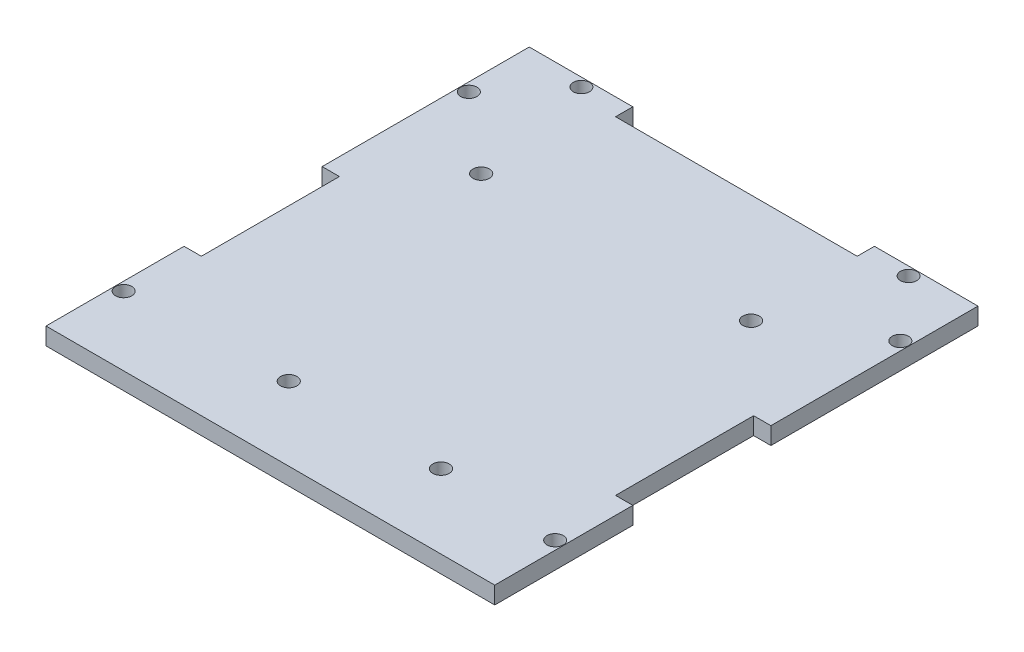
SolidWorks part; units mm, degrees
ref_plane "Front Plane" through (0, 0, 0) normal (0, 0, 1) x (1, 0, 0)
ref_plane "Top Plane" through (0, 0, 0) normal (0, 1, 0) x (1, 0, 0)
ref_plane "Right Plane" through (0, 0, 0) normal (1, 0, 0) x (0, 0, -1)
sketch "Sketch1" plane through (0, 0, 0) normal (0, 1, 0) x (1, 0, 0)
  line L0 (-41.275, 0) -> (-36.3683, -11.7139)
  line L1 (-10.2051, 85.725) -> (10.2051, 85.725)
  line L3 (-41.275, 88.9) -> (-22.225, 88.9)
  line L4 (22.225, 88.9) -> (22.225, 85.725)
  line L5 (41.275, 50.8) -> (41.275, 88.9)
  line L6 (-41.275, 0) -> (-38.1, 0) construction
  line L7 (-41.275, 50.8) -> (-38.1, 50.8)
  line L8 (0, 63.5) -> (0, -63.5) construction
  line L9 (38.1, 50.8) -> (38.1, 25.4)
  line L10 (-38.1, 50.8) -> (-38.1, 25.4)
  line L11 (-41.275, 50.8) -> (-41.275, 88.9)
  line L12 (41.275, 50.8) -> (38.1, 50.8)
  line L13 (-22.225, 88.9) -> (-22.225, 85.725)
  line L14 (-22.225, 85.725) -> (-10.2051, 85.725)
  line L16 (41.275, 88.9) -> (22.225, 88.9)
  line L17 (-41.275, 0) -> (41.275, 0) construction
  line L18 (-38.1, 0) -> (-38.1, 25.4) construction
  line L19 (-38.1, 25.4) -> (-41.275, 25.4)
  line L21 (-41.275, 0) -> (-41.275, 25.4)
  line L22 (38.1, 25.4) -> (41.275, 25.4)
  line L23 (-38.1, 0) -> (-33.467, -10.4244) construction
  line L24 (41.275, 0) -> (41.275, 25.4)
  line L25 (33.467, -10.4244) -> (38.1, 0) construction
  line L26 (-36.3683, -11.7139) -> (-33.467, -10.4244) construction
  line L27 (41.275, 0) -> (36.3683, -11.7139)
  line L28 (36.3683, -11.7139) -> (33.467, -10.4244) construction
  line L29 (-17.858, -45.5446) -> (-12.7, -57.15) construction
  line L30 (-12.7, -57.15) -> (-15.6014, -58.4395) construction
  line L31 (-17.858, -45.5446) -> (-20.7593, -46.8341)
  line L32 (-15.6014, -58.4395) -> (-20.7593, -46.8341)
  line L33 (12.7, -57.15) -> (17.858, -45.5446) construction
  line L34 (-33.467, -10.4244) -> (-17.858, -45.5446)
  line L35 (-12.7, -57.15) -> (12.7, -57.15) construction
  line L36 (17.858, -45.5446) -> (33.467, -10.4244)
  line L38 (41.275, 69.85) -> (-41.275, 69.85) construction
  line L39 (12.7, -57.15) -> (15.6014, -58.4395) construction
  line L40 (17.858, -45.5446) -> (20.7593, -46.8341)
  line L41 (15.6014, -58.4395) -> (20.7593, -46.8341)
  line L42 (38.1, 0) -> (38.1, 25.4) construction
  line L43 (-15.6014, -58.4395) -> (-12.7, -60.325)
  line L44 (-5.08, -57.15) -> (-12.7, -57.15) construction
  line L45 (-5.08, -57.15) -> (-5.08, -60.325)
  line L46 (-5.08, -60.325) -> (-12.7, -60.325)
  line L47 (-12.7, -57.15) -> (-12.7, -60.325) construction
  line L48 (5.08, -57.15) -> (12.7, -57.15) construction
  line L49 (5.08, -57.15) -> (5.08, -60.325)
  line L50 (5.08, -60.325) -> (12.7, -60.325)
  line L51 (12.7, -57.15) -> (12.7, -60.325) construction
  line L52 (15.6014, -58.4395) -> (12.7, -60.325)
  line L53 (-5.08, -57.15) -> (5.08, -57.15)
  line L54 (33.467, -10.4244) -> (36.3683, -11.7139)
  line L55 (-33.467, -10.4244) -> (-36.3683, -11.7139)
  line L56 (10.2051, 85.725) -> (22.225, 85.725)
  point P0 (0, 0)
  point P1 (0, -57.15)
  dimension "D1" = 25.4
  dimension "D2" = 57.15
  dimension "D3" = 3.175
  dimension "D4" = 82.55
  dimension "D5" = 3.175
  dimension "D6" = 44.45
  dimension "D8" = 38.1
  dimension "D9" = 50.8
  dimension "D10" = 25.4
  dimension "D11" = 12.7
  dimension "D12" = 12.7
  dimension "D13" = 10.16
extrude "Boss-Extrude1" add sketch "Sketch1" along normal blind 3.175
sketch "Sketch2" plane through (0, 0, 0) normal (0, -1, 0) x (-1, 0, 0)
  line L0 (39.6875, 50.8) -> (39.6875, 88.9) construction
  line L1 (41.275, 50.8) -> (38.1, 50.8) construction
  line L2 (22.225, 88.9) -> (41.275, 88.9) construction
  line L3 (0, 85.725) -> (0, -57.15) construction
  line L6 (-5.08, -58.7375) -> (-15.1428, -58.7375) construction
  line L7 (5.08, -57.15) -> (-5.08, -57.15) construction
  line L8 (-22.225, 85.725) -> (22.225, 85.725) construction
  line L10 (22.225, 88.9) -> (41.275, 88.9) construction
  line L11 (39.6875, 25.4) -> (39.6875, -3.7899) construction
  line L12 (38.1, 25.4) -> (41.275, 25.4) construction
  line L15 (41.275, 0) -> (36.3683, -11.7139) construction
  line L18 (34.9176, -11.0691) -> (41.275, 3.235) construction
  line L23 (36.3683, -11.7139) -> (33.467, -10.4244) construction
  line L24 (41.275, 25.4) -> (41.275, 0) construction
  line L25 (19.3086, -46.1893) -> (13.0261, -60.325) construction
  line L26 (17.858, -45.5446) -> (20.7593, -46.8341) construction
  line L27 (12.7, -60.325) -> (5.08, -60.325) construction
  line L28 (5.08, -58.7375) -> (15.1428, -58.7375) construction
  line L29 (5.08, -60.325) -> (5.08, -57.15) construction
  line L30 (15.6014, -58.4395) -> (12.7, -60.325) construction
  line L31 (-19.3086, -46.1893) -> (-13.0261, -60.325) construction
  line L32 (-34.9176, -11.0691) -> (-41.275, 3.235) construction
  line L33 (-39.6875, 25.4) -> (-39.6875, -3.7899) construction
  line L34 (-39.6875, 50.8) -> (-39.6875, 88.9) construction
  circle A0 centre (39.6875, 76.2) radius 1.5
  circle A1 centre (-8.89, -58.7375) radius 1.5
  circle A2 centre (39.6875, 12.7) radius 1.5
  circle A3 centre (37.4966, -5.2664) radius 1.5
  circle A4 centre (16.7297, -51.992) radius 1.5
  circle A5 centre (8.89, -58.7375) radius 1.5
  circle A6 centre (-16.7297, -51.992) radius 1.5
  circle A7 centre (-37.4966, -5.2664) radius 1.5
  circle A8 centre (-39.6875, 12.7) radius 1.5
  circle A9 centre (-39.6875, 76.2) radius 1.5
  dimension "D1" = 3
  dimension "D4" = 6.35
  dimension "D6" = 3.81
  dimension "D2" = 3
  dimension "D3" = 12.7
  dimension "D5" = 6.35
  dimension "D7" = 12.7
extrude "Cut-Extrude1" cut sketch "Sketch2" against normal through all
sketch "Sketch5" plane through (0, 3.175, 0) normal (0, 1, 0) x (1, 0, 0)
  line L0 (-41.275, 25.4) -> (-41.275, 0) construction
  line L1 (41.275, 0) -> (-41.275, 0)
  line L2 (41.275, 0) -> (41.275, -60.325)
  line L3 (41.275, -60.325) -> (-41.275, -60.325)
  line L4 (-41.275, 0) -> (-41.275, -60.325)
  line L5 (-12.7, -60.325) -> (-5.08, -60.325) construction
extrude "Cut-Extrude4" cut sketch "Sketch5" against normal through all
sketch "Sketch6" plane through (0, 3.175, 0) normal (0, 1, 0) x (1, 0, 0)
  line L0 (-22.225, 87.3125) -> (-41.275, 87.3125) construction
  line L1 (-22.225, 85.725) -> (-22.225, 88.9) construction
  line L2 (-41.275, 88.9) -> (-41.275, 50.8) construction
  line L3 (22.225, 87.3125) -> (41.275, 87.3125) construction
  line L4 (22.225, 88.9) -> (22.225, 85.725) construction
  line L5 (41.275, 50.8) -> (41.275, 88.9) construction
  circle A0 centre (-30.099, 87.3125) radius 1.5
  circle A1 centre (30.099, 87.3125) radius 1.5
  dimension "D1" = 3
  dimension "D2" = 3
  dimension "D3" = 7.874
  dimension "D4" = 7.874
extrude "Cut-Extrude5" cut sketch "Sketch6" against normal through all
ref_plane "Plane1" through (1.049, -3, -53.8879) normal (0, 1, 0) x (1, 0, 0)
sketch "Sketch9" plane through (0, 3.175, 0) normal (0, 1, 0) x (1, 0, 0)
  circle A0 centre (17.7836, 13.6043) radius 1.51
  circle A1 centre (-10.1564, 13.5366) radius 1.51
  circle A2 centre (-25.5193, 64.2996) radius 1.51
  circle A3 centre (22.7375, 65.6864) radius 1.51
  point P6 (-25.5193, 64.2996)
  point P9 (22.7375, 65.6864)
  dimension "D1" = 3.02
extrude "Cut-Extrude6" cut sketch "Sketch9" against normal through all
